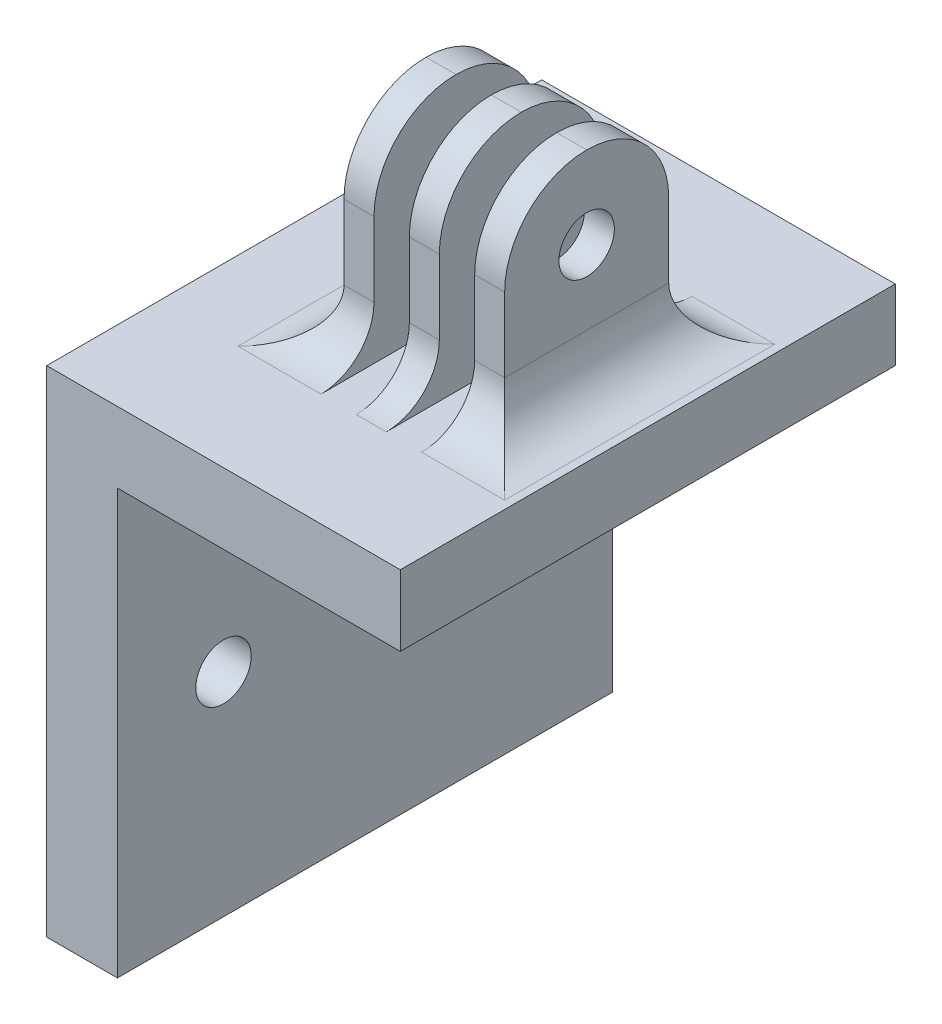
SolidWorks part; units mm, degrees
material "Nylon 6/10"
ref_plane "Front Plane" through (0, 0, 0) normal (0, 0, 1) x (1, 0, 0)
ref_plane "Top Plane" through (0, 0, 0) normal (0, 1, 0) x (1, 0, 0)
ref_plane "Right Plane" through (0, 0, 0) normal (1, 0, 0) x (0, 0, -1)
sketch "Sketch1" plane through (0, 0, 0) normal (1, 0, 0) x (0, 0, -1)
  line L0 (-22.225, -3.175) -> (22.225, -3.175) construction
  line L1 (-22.225, -22.225) -> (22.225, -22.225)
  line L2 (-22.225, -22.225) -> (-22.225, 22.225)
  line L3 (-22.225, 22.225) -> (22.225, 22.225)
  line L4 (22.225, -22.225) -> (22.225, 22.225)
  line L5 (-22.225, -22.225) -> (22.225, 22.225) construction
  line L6 (-22.225, 22.225) -> (22.225, -22.225) construction
  line L7 (22.225, 15.875) -> (-22.225, 15.875) construction
  circle A0 centre (-12.7, -3.175) radius 2.4892
  circle A1 centre (12.7, -3.175) radius 2.4892
  point P0 (0, 0)
  dimension "D4" = 25.4
  dimension "D5" = 9.525
  dimension "D6" = 4.9784
  dimension "D1" = 19.05
  dimension "D2" = 44.45
  dimension "D3" = 6.35
  dimension "D7" = 19.05
extrude "Boss-Extrude1" add sketch "Sketch1" along normal blind 6.35
sketch "Sketch2" plane through (6.35, 0, 0) normal (1, 0, 0) x (0, 0, -1)
  line L0 (22.225, -22.225) -> (22.225, 22.225) construction
  line L1 (-22.225, 22.225) -> (22.225, 22.225)
  line L2 (-22.225, 22.225) -> (-22.225, 15.875)
  line L3 (-22.225, 15.875) -> (22.225, 15.875)
  line L4 (22.225, 22.225) -> (22.225, 15.875)
  dimension "D1" = 6.35
extrude "Boss-Extrude2" add sketch "Sketch2" along normal blind 25.4
sketch "Sketch3" plane through (0, 22.225, 0) normal (0, 1, 0) x (1, 0, 0)
  line L0 (13.1826, 22.225) -> (13.1826, -22.225) construction
  line L1 (31.75, 22.225) -> (0, 22.225) construction
  line L2 (31.75, -22.225) -> (0, -22.225) construction
  line L3 (31.75, 22.225) -> (31.75, -22.225) construction
  line L4 (0, 0) -> (31.75, 0) construction
  line L5 (11.8364, -7.366) -> (14.5288, -7.366)
  line L6 (11.8364, -7.366) -> (11.8364, 7.366)
  line L7 (11.8364, 7.366) -> (14.5288, 7.366)
  line L8 (14.5288, -7.366) -> (14.5288, 7.366)
  line L9 (11.8364, -7.366) -> (14.5288, 7.366) construction
  line L10 (11.8364, 7.366) -> (14.5288, -7.366) construction
  line L11 (0, 22.225) -> (0, -22.225) construction
  line L12 (20.3962, -7.366) -> (20.3962, 7.366)
  line L13 (17.7038, 7.366) -> (20.3962, 7.366)
  line L14 (17.7038, -7.366) -> (17.7038, 7.366)
  line L15 (17.7038, -7.366) -> (20.3962, -7.366)
  line L16 (26.2636, -7.366) -> (26.2636, 7.366)
  line L17 (23.5712, 7.366) -> (26.2636, 7.366)
  line L18 (23.5712, -7.366) -> (23.5712, 7.366)
  line L19 (23.5712, -7.366) -> (26.2636, -7.366)
  line L20 (19.05, 7.366) -> (19.05, 22.225) construction
  point P8 (13.1826, 0)
  dimension "D1" = 12.7
  dimension "D2" = 2.6924
  dimension "D3" = 14.732
  dimension "D5" = 3.175
  dimension "D4" = 3
extrude "Boss-Extrude3" add sketch "Sketch3" along normal blind 18.796
fillet "Fillet3" radius 7.366 6 edges at (19.05, 41.021, -7.366) (13.1826, 41.021, -7.366) (24.9174, 41.021, 7.366) (19.05, 41.021, 7.366) (13.1826, 41.021, 7.366) (24.9174, 41.021, -7.366)
sketch "Sketch4" plane through (11.8364, 0, 0) normal (-1, 0, 0) x (0, 0, 1)
  circle A0 centre (0, 33.655) radius 2.4892
  dimension "D1" = 4.9784
extrude "Cut-Extrude1" cut sketch "Sketch4" against normal up to surface (14.4272 mm away) contours A0 up to face at (26.2636, 31.1664, 0)
fillet "Fillet4" radius 4.7625 8 edges at (13.1826, 22.225, -7.366) (19.05, 22.225, -7.366) (24.9174, 22.225, -7.366) (26.2636, 22.225, 0) (24.9174, 22.225, 7.366) (19.05, 22.225, 7.366) (11.8364, 22.225, 0) (13.1826, 22.225, 7.366)
